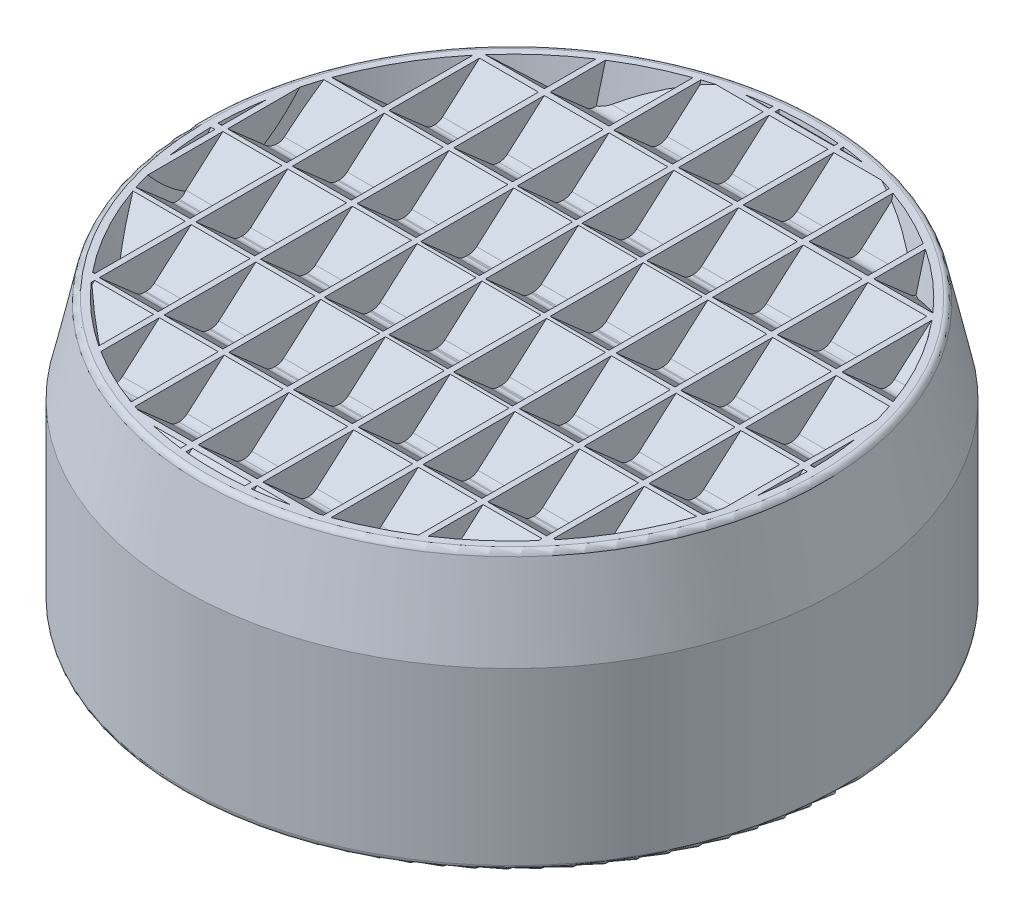
SolidWorks part; units mm, degrees
ref_plane "Front" through (0, 0, 0) normal (0, 0, 1) x (1, 0, 0)
ref_plane "Top" through (0, 0, 0) normal (0, 1, 0) x (1, 0, 0)
ref_plane "Right" through (0, 0, 0) normal (1, 0, 0) x (0, 0, -1)
sketch "Sketch1" plane through (0, 0, 0) normal (0, 1, 0) x (1, 0, 0)
  circle A0 centre (0, 0) radius 2.8
  dimension "D1" = 5.6
extrude "Boss-Extrude1" add sketch "Sketch1" along normal blind 1.5
sketch "Sketch2" plane through (0, 1.5, 0) normal (0, 1, 0) x (1, 0, 0)
  circle A1 centre (0, 0) radius 2.8
  circle A2 centre (0, 0) radius 2.8
  dimension "D1" = 0
extrude "Boss-Extrude2" add sketch "Sketch2" along normal blind 0.75 draft 12.5
sketch "Sketch3" plane through (0, 0, 0) normal (1, 0, 0) x (0, 0, -1)
  line L0 (2.4337, 2.25) -> (2.1196, 1.9748)
  line L1 (2.6337, 2.25) -> (-2.6337, 2.25) construction
  line L2 (1.9878, 1.9748) -> (1.6737, 2.25)
  line L3 (2.4337, 2.25) -> (1.6737, 2.25)
  line L4 (1.6137, 2.25) -> (1.2996, 1.9748)
  line L5 (1.1678, 1.9748) -> (0.8537, 2.25)
  line L6 (1.6137, 2.25) -> (0.8537, 2.25)
  line L7 (0.7937, 2.25) -> (0.4796, 1.9748)
  line L8 (0.3478, 1.9748) -> (0.0337, 2.25)
  line L9 (0.7937, 2.25) -> (0.0337, 2.25)
  line L10 (-0.0263, 2.25) -> (-0.3404, 1.9748)
  line L11 (-0.4722, 1.9748) -> (-0.7863, 2.25)
  line L12 (-0.0263, 2.25) -> (-0.7863, 2.25)
  line L13 (-0.8463, 2.25) -> (-1.1604, 1.9748)
  line L14 (-1.2922, 1.9748) -> (-1.6063, 2.25)
  line L15 (-0.8463, 2.25) -> (-1.6063, 2.25)
  arc A0 (2.1196, 1.9748) -> (1.9878, 1.9748) centre (2.0537, 2.05) cw
  arc A1 (1.2996, 1.9748) -> (1.1678, 1.9748) centre (1.2337, 2.05) cw
  arc A2 (0.4796, 1.9748) -> (0.3478, 1.9748) centre (0.4137, 2.05) cw
  arc A3 (-0.3404, 1.9748) -> (-0.4722, 1.9748) centre (-0.4063, 2.05) cw
  arc A4 (-1.1604, 1.9748) -> (-1.2922, 1.9748) centre (-1.2263, 2.05) cw
  point P9 (2.0537, 1.95)
  dimension "D3" = 0.1
  dimension "D1" = 0.76
  dimension "D2" = 0.2
  dimension "D5" = 0.3
  dimension "D4" = 5
extrude "Cut-Extrude1" cut sketch "Sketch3" against normal mid plane 0.5 contours A2 L7 L9 L8 region at (0, 2.1415, -0.4137)
extrude "Cut-Extrude2" cut sketch "Sketch3<3>" against normal mid plane 0.5 contours L6 L5 A1 L4
sketch "Sketch3<3>" plane through (0, 0, 0) normal (1, 0, 0) x (0, 0, -1) same geometry as "Sketch3"
extrude "Cut-Extrude3" cut sketch "Sketch3<4>" against normal mid plane 0.5 contours L2 L3 L0 A0
sketch "Sketch3<4>" plane through (0, 0, 0) normal (1, 0, 0) x (0, 0, -1) same geometry as "Sketch3"
extrude "Cut-Extrude4" cut sketch "Sketch3<5>" against normal mid plane 0.5 contours L11 L12 L10 A3
sketch "Sketch3<5>" plane through (0, 0, 0) normal (1, 0, 0) x (0, 0, -1) same geometry as "Sketch3"
extrude "Cut-Extrude5" cut sketch "Sketch3<6>" against normal mid plane 0.5 contours L15 L14 A4 L13
sketch "Sketch3<6>" plane through (0, 0, 0) normal (1, 0, 0) x (0, 0, -1) same geometry as "Sketch3"
pattern_linear "LPattern1" count 2 spacing 0.55 along (1, 0, 0) count 2 spacing 0.55 along (-1, 0, 0) of "Cut-Extrude2", "Cut-Extrude3", "Cut-Extrude4", "Cut-Extrude5", "Cut-Extrude1" pattern seed only yes
pattern_linear "LPattern2" count 2 spacing 1.1 along (1, 0, 0) count 2 spacing 1.1 along (-1, 0, 0) of "Cut-Extrude1", "Cut-Extrude2", "Cut-Extrude4", "Cut-Extrude5", "Cut-Extrude3" pattern seed only yes
pattern_linear "LPattern3" count 2 spacing 1.65 along (1, 0, 0) count 2 spacing 1.65 along (-1, 0, 0) of "Cut-Extrude1", "Cut-Extrude2", "Cut-Extrude4", "Cut-Extrude3", "Cut-Extrude5" pattern seed only yes
pattern_linear "LPattern4" count 2 spacing 2.2 along (1, 0, 0) count 2 spacing 2.2 along (-1, 0, 0) of "Cut-Extrude1", "Cut-Extrude2", "Cut-Extrude4" pattern seed only yes
pattern_linear "LPattern5" count 3 spacing 0.81 along (0, 0, 1) of "Cut-Extrude5", "LPattern1", "LPattern2", "LPattern3", "LPattern4"
pattern_linear "LPattern6" count 2 spacing 0.81 along (0, 0, -1) of "Cut-Extrude3", "LPattern1"
pattern_linear "LPattern7" count 2 spacing 2.75 along (1, 0, 0) count 2 spacing 2.75 along (-1, 0, 0) of "Cut-Extrude1", "Cut-Extrude2", "Cut-Extrude4" pattern seed only yes
sketch "Sketch4" plane through (0, 2.25, 0) normal (0, 1, 0) x (1, 0, 0)
  circle A0 centre (0, 0) radius 2.6337
  circle A1 centre (0, 0) radius 2.5337
  circle A2 centre (0, 0) radius 2.6337 construction
  dimension "D1" = 0.1
extrude "Boss-Extrude3" add sketch "Sketch4" against normal blind 0.75 draft 12.5 draft outward yes
fillet "Fillet1" radius 0.05 2 edges at (0, 0, 2.8) (0, 2.25, 2.6337)
